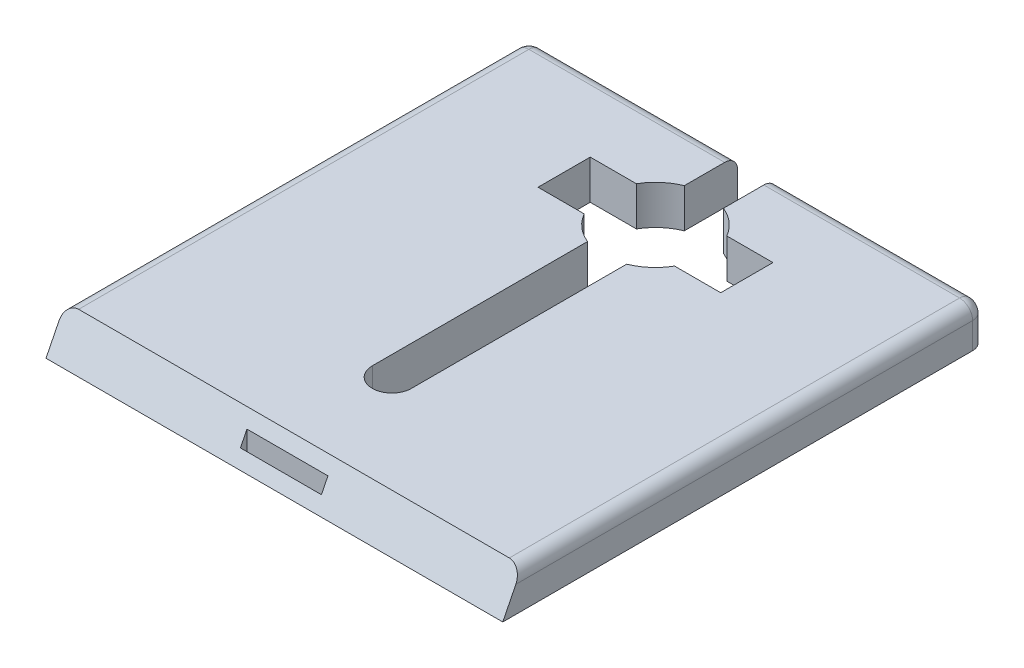
SolidWorks part; units mm, degrees
ref_plane "Ebene vorne" through (0, 0, 0) normal (0, 0, 1) x (1, 0, 0)
ref_plane "Ebene oben" through (0, 0, 0) normal (0, 1, 0) x (1, 0, 0)
ref_plane "Ebene rechts" through (0, 0, 0) normal (1, 0, 0) x (0, 0, -1)
sketch "Skizze1" plane through (0, 0, 0) normal (0, 1, 0) x (1, 0, 0)
  line L1 (-8.75, -9.25) -> (8.75, -9.25)
  line L2 (-8.75, -9.25) -> (-8.75, 9.25)
  line L3 (-8.75, 9.25) -> (8.75, 9.25)
  line L4 (8.75, -9.25) -> (8.75, 9.25)
  line L5 (-8.75, -9.25) -> (8.75, 9.25) construction
  line L6 (-8.75, 9.25) -> (8.75, -9.25) construction
  point P0 (0, 0)
  dimension "D1" = 18.5
  dimension "D2" = 17.5
extrude "Aufsatz-Linear austragen1" add sketch "Skizze1" along normal blind 1.5
fillet "Verrundung1" radius 0.5 3 edges at (8.75, 1.5, 0) (0, 1.5, -9.25) (-8.75, 1.5, 0)
sketch "Skizze2" plane through (-8.75, 0, 0) normal (-1, 0, 0) x (0, 0, 1)
  line L0 (9.25, 0) -> (8.5, 1.5)
  line L1 (-8.75, 1.5) -> (9.25, 1.5) construction
  line L2 (8.5, 1.5) -> (9.25, 1.5)
  line L3 (9.25, 1.5) -> (9.25, 0)
  dimension "D1" = 0.75
extrude "Schnitt-Linear austragen1" cut sketch "Skizze2" against normal up to surface (17.5 mm away) up to face at (8.75, 0.5, 0)
fillet "Verrundung2" radius 0.5 4 edges at (8.6036, 1.3536, -9.1036) (-8.6036, 1.3536, -9.1036) (8.75, 0.5, -9.25) (-8.75, 0.5, -9.25)
sketch "Skizze5" plane through (0, 1.5, 0) normal (0, 1, 0) x (1, 0, 0)
  line L0 (-8.75, 8.75) -> (-8.75, -9.25) construction
  line L1 (-3.5, 4.35) -> (3.5, 4.35)
  line L2 (-3.5, 4.35) -> (-3.5, 6.35)
  line L3 (-3.5, 6.35) -> (3.5, 6.35)
  line L4 (3.5, 4.35) -> (3.5, 6.35)
  line L5 (-3.5, 4.35) -> (3.5, 6.35) construction
  line L6 (-3.5, 6.35) -> (3.5, 4.35) construction
  line L7 (-8.25, 9.25) -> (8.25, 9.25) construction
  circle A0 centre (0, 5.35) radius 2
  dimension "D2" = 4
  dimension "D1" = 7
  dimension "D3" = 2
  dimension "D4" = 8.75
  dimension "D5" = 3.9
extrude "Schlüsselloch" cut sketch "Skizze5" against normal up to surface (1.5 mm away) contours A0 L3 L2 L1 | L3 A0 | L1 A0 L3 | L1 A0 | A0 L1 L4 L3 region at (-2.7046, 1.5, -5.35) region at (0, 1.5, -5.35) region at (0, 1.5, -3.94) region at (2.7046, 1.5, -5.35) region at (0, 1.5, -6.76) up to face at (0, 0, -2.9512)
sketch "Skizze6" plane through (0, 1.5, 0) normal (0, 1, 0) x (1, 0, 0)
  line L0 (8.25, -8.5) -> (-8.25, -8.5) construction
  line L1 (-1.5515, -9) -> (1.5515, -9)
  line L2 (-1.5515, -9) -> (-1.5515, -8.75)
  line L3 (-1.5515, -8.75) -> (1.5515, -8.75)
  line L4 (1.5515, -9) -> (1.5515, -8.75)
  line L5 (-1.5515, -9) -> (1.5515, -8.75) construction
  line L6 (-1.5515, -8.75) -> (1.5515, -9) construction
  line L7 (-8.75, -8.75) -> (-8.75, -9.25) construction
  point P0 (0, -8.875)
  dimension "D1" = 0.25
  dimension "D2" = 0.25
  dimension "D3" = 8.75
extrude "Griff" cut sketch "Skizze6" against normal up to surface (1.5 mm away) up to face at (0, 0, -5.35)
sketch "Skizze7" plane through (0, 1.5, 0) normal (0, 1, 0) x (1, 0, 0)
  line L5 (0, 9.25) -> (0, -4.75) construction
  line L6 (-8.25, 9.25) -> (8.25, 9.25) construction
  line L7 (0.75, 9.25) -> (0.75, -4.75)
  line L8 (-0.75, 9.25) -> (-0.75, -4.75)
  arc A0 (0.75, 9.25) -> (-0.75, 9.25) centre (0, 9.25) ccw
  arc A1 (-0.75, -4.75) -> (0.75, -4.75) centre (0, -4.75) ccw
  point P4 (0, 2.25)
  dimension "D1" = 14
  dimension "D2" = 1.5
extrude "Langloch_Antenne" cut sketch "Skizze7" against normal up to surface (1.5 mm away) up to face at (0, 0, 8.875)
